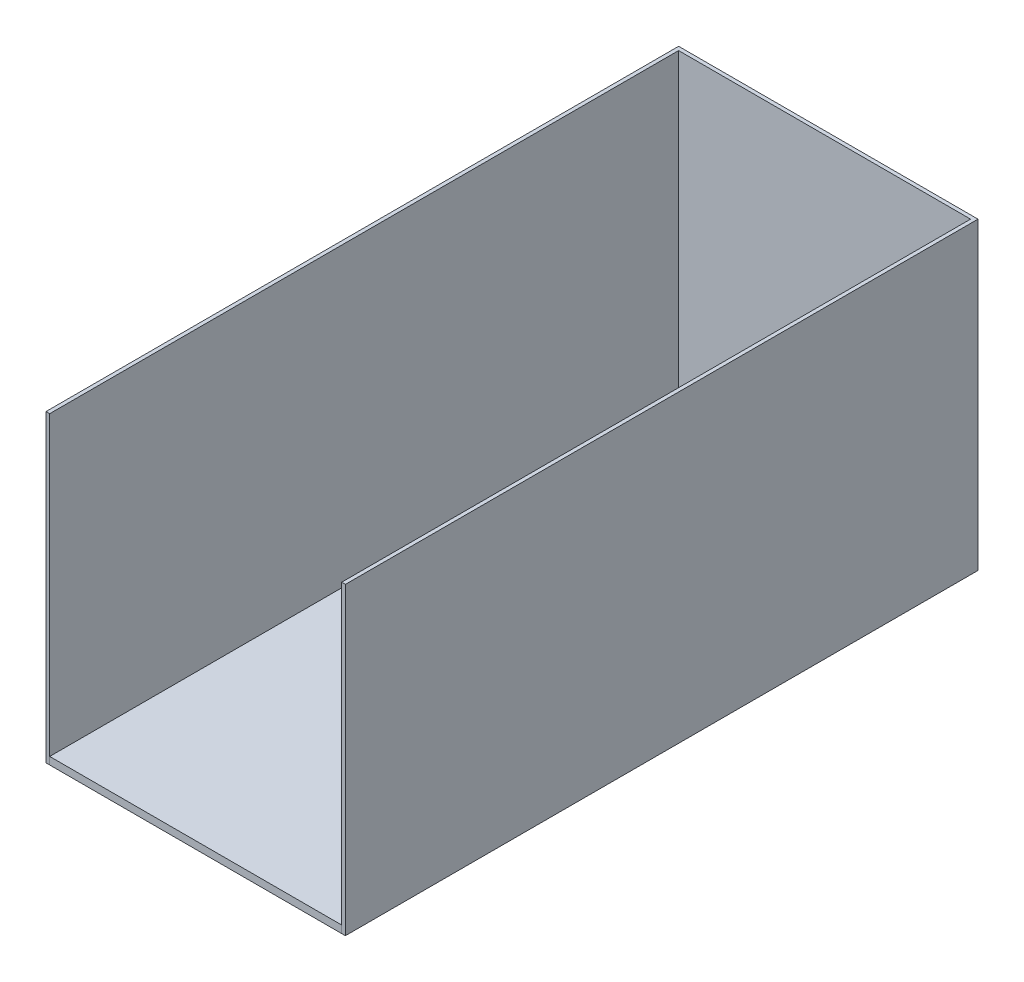
SolidWorks part; units mm, degrees
ref_plane "Front Plane" through (0, 0, 0) normal (0, 0, 1) x (1, 0, 0)
ref_plane "Top Plane" through (0, 0, 0) normal (0, 1, 0) x (1, 0, 0)
ref_plane "Right Plane" through (0, 0, 0) normal (1, 0, 0) x (0, 0, -1)
sketch "Sketch1" plane through (0, 0, 0) normal (0, 1, 0) x (1, 0, 0)
  line L0 (1992, 0) -> (1992, 4262)
  line L1 (0, 0) -> (1967, 0)
  line L2 (0, 0) -> (0, 4237)
  line L3 (0, 4237) -> (1967, 4237)
  line L4 (1967, 0) -> (1967, 4237)
  line L5 (-25, 4262) -> (1992, 4262)
  line L6 (-25, 0) -> (-25, 4262)
  line L7 (-25, 0) -> (1992, 0)
  point P9 (0, 0)
  point P10 (1992, 4262)
  point P11 (0, 0)
  point P12 (0, 0)
  point P13 (0, 0)
  point P14 (0, 0)
  point P15 (0, 0)
  dimension "D1" = 1967
  dimension "D2" = 4237
  dimension "D3" = 25
extrude "Boss-Extrude1" add sketch "Sketch1" along normal blind 50 contours L2 L1 L4 L3
extrude "Boss-Extrude2" add sketch "Sketch1<7>" along normal blind 2050 separate body contours L6 L7 L2 L3 L4 L0 L5 region at (1979.5, 0, -47.1518)
sketch "Sketch1<7>" plane through (0, 0, 0) normal (0, 1, 0) x (1, 0, 0) same geometry as "Sketch1"
equation "\"van_w\"=1967"
equation "\"D1@Sketch1\"=\"van_w\""
equation "\"van_l\"=4237"
equation "\"D2@Sketch1\"=\"van_l\""
equation "\"van_h\"=2050"
equation "\"D1@Boss-Extrude2\"=\"van_h\""
